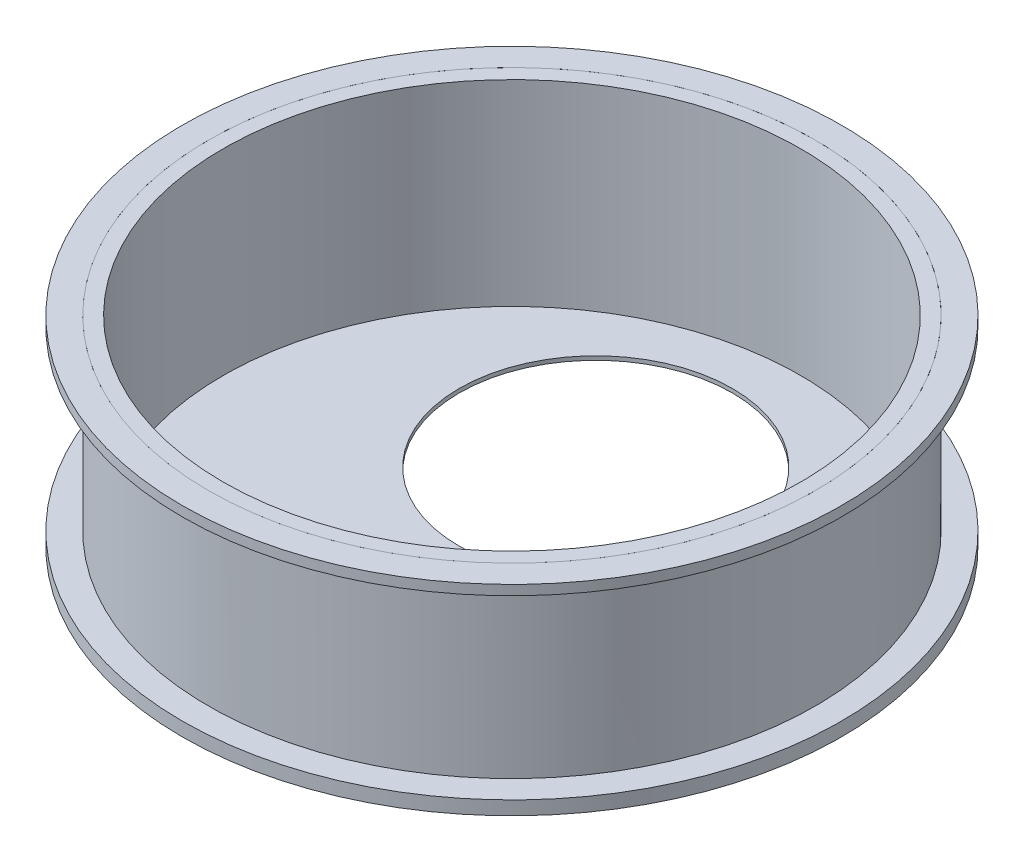
SolidWorks part; units mm, degrees
ref_plane "Front Plane" through (0, 0, 0) normal (0, 0, 1) x (1, 0, 0)
ref_plane "Top Plane" through (0, 0, 0) normal (0, 1, 0) x (1, 0, 0)
ref_plane "Right Plane" through (0, 0, 0) normal (1, 0, 0) x (0, 0, -1)
sketch "Sketch1" plane through (0, 0, 0) normal (0, 1, 0) x (1, 0, 0)
  circle A0 centre (0, 0) radius 1545
  circle A1 centre (0, 0) radius 1470
extrude "Boss-Extrude1" add sketch "Sketch1" along normal blind 500
ref_plane "Plane1" through (0, 500, 0) normal (0, 1, 0) x (1, 0, 0)
sketch "Sketch2" plane through (0, 500, 0) normal (0, 1, 0) x (1, 0, 0)
  circle A0 centre (0, 0) radius 1677.7105
  circle A1 centre (0, 0) radius 1545
  circle A2 centre (0, 0) radius 1545
  dimension "D1" = 0
extrude "Boss-Extrude3" add sketch "Sketch2" against normal blind 50 separate body
mirror "Mirror1" about plane through (0, 0, 0) normal (0, 1, 0) of "Boss-Extrude1", "Boss-Extrude3"
ref_plane "Plane2" through (0, -500, 0) normal (0, -1, 0) x (-1, 0, 0)
sketch "Sketch4" plane through (0, -500, 0) normal (0, -1, 0) x (-1, 0, 0)
  circle A0 centre (0, 0) radius 1677.7105 construction
  circle A1 centre (0, 0) radius 1677.7105
extrude "Boss-Extrude4" add sketch "Sketch4" along normal blind 20
sketch "Sketch5" plane through (0, -520, 0) normal (0, -1, 0) x (-1, 0, 0)
  circle A0 centre (116.8011, -733.8017) radius 435.484
  circle A1 centre (116.8011, 543.6166) radius 695.291
extrude "Cut-Extrude1" cut sketch "Sketch5" against normal blind 265
